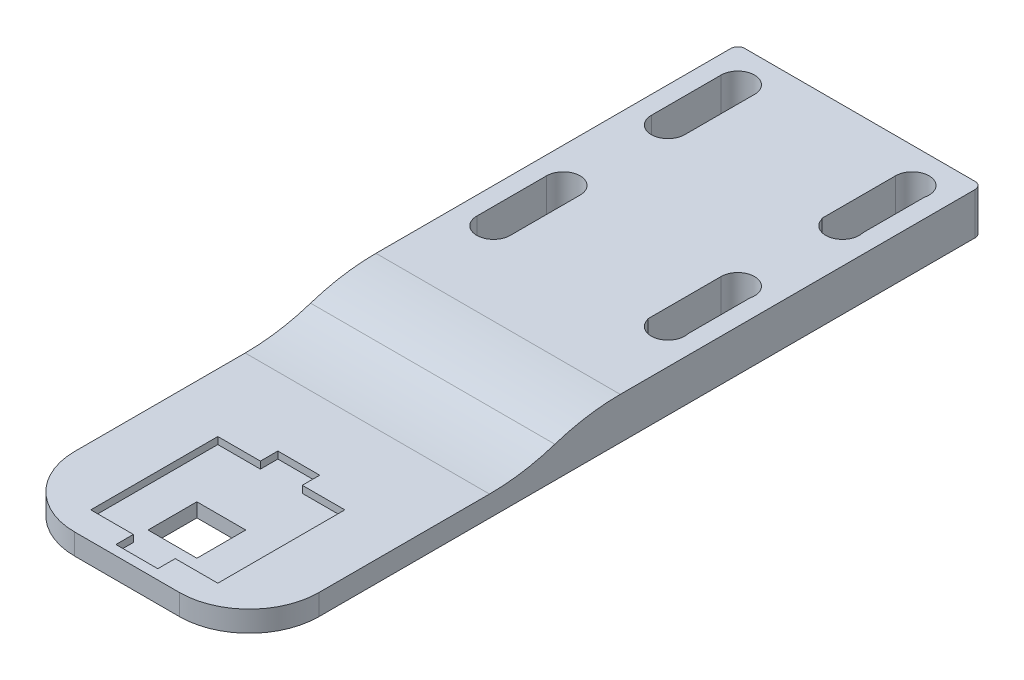
SolidWorks part; units mm, degrees
ref_plane "Front Plane" through (0, 0, 0) normal (0, 0, 1) x (1, 0, 0)
ref_plane "Top Plane" through (0, 0, 0) normal (0, 1, 0) x (1, 0, 0)
ref_plane "Right Plane" through (0, 0, 0) normal (1, 0, 0) x (0, 0, -1)
sketch "Sketch1" plane through (0, 0, 0) normal (0, 1, 0) x (1, 0, 0)
  line L1 (-17.3881, 19.9254) -> (17.6119, 19.9254)
  line L2 (-17.3881, 19.9254) -> (-17.3881, -85.0746)
  line L3 (-17.3881, -85.0746) -> (17.6119, -85.0746)
  line L4 (17.6119, 19.9254) -> (17.6119, -85.0746)
  dimension "D1" = 35
  dimension "D2" = 105
extrude "Boss-Extrude1" add sketch "Sketch1" along normal blind 6
sketch "Sketch2" plane through (0, 6, 0) normal (0, 1, 0) x (1, 0, 0)
  line L0 (17.6119, 19.9254) -> (-17.3881, 19.9254) construction
  line L1 (12.6119, -10.0746) -> (-12.3881, -10.0746)
  line L2 (12.6119, -10.0746) -> (12.6119, 14.9254)
  line L3 (12.6119, 14.9254) -> (-12.3881, 14.9254)
  line L4 (-12.3881, -10.0746) -> (-12.3881, 14.9254)
  line L5 (12.6119, -10.0746) -> (-12.3881, 14.9254) construction
  line L6 (12.6119, 14.9254) -> (-12.3881, -10.0746) construction
  point P0 (0.1119, 2.4254)
  point P7 (0.1119, 19.9254)
  dimension "D1" = 25
  dimension "D2" = 25
  dimension "D3" = 0
  dimension "D4" = 5
hole_wizard "M4 Clearance Hole1" positions "Sketch3" profile "Sketch4" hole size "M4" standard "ANSI Metric" end condition through all
sketch "Sketch3" plane through (0, 6, 0) normal (0, 1, 0) x (1, 0, 0)
  point P0 (-12.3881, 14.9254)
  point P3 (12.6119, 14.9254)
  point P6 (12.6119, -10.0746)
  point P9 (-12.3881, -10.0746)
sketch "Sketch4" plane through (-12.3881, 6, -14.9254) normal (1, 0, 0) x (0, 0, 1)
  line L0 (0, 0) -> (0, 6)
  line L1 (0, 6) -> (2.4, 6)
  line L2 (2.4, 6) -> (2.4, 0)
  line L5 (2.4, 0) -> (0, 0)
  line L11 (0, -6.35) -> (0, 107.95) construction
  dimension "Thru Hole Dia." = 4.8
  dimension "Thru Hole Depth" = 6
pattern_linear "LPattern2" count 2 spacing 10 along (0, 0, 1) of "M4 Clearance Hole1"
sketch "Sketch5" plane through (0, 6, 0) normal (0, 1, 0) x (1, 0, 0)
  line L1 (-14.7881, 14.9254) -> (-9.9881, 14.9254)
  line L2 (-14.7881, 14.9254) -> (-14.7881, 4.9254)
  line L3 (-14.7881, 4.9254) -> (-9.9881, 4.9254)
  line L4 (-9.9881, 14.9254) -> (-9.9881, 4.9254)
  line L5 (-14.7881, -10.0746) -> (-9.9881, -10.0746)
  line L6 (-14.7881, -10.0746) -> (-14.7881, -20.0746)
  line L7 (-14.7881, -20.0746) -> (-9.9881, -20.0746)
  line L8 (-9.9881, -10.0746) -> (-9.9881, -20.0746)
  line L9 (10.2119, 14.9254) -> (14.9426, 14.9254)
  line L10 (10.2119, 14.9254) -> (10.2119, 4.3527)
  line L11 (10.2119, 4.3527) -> (14.9426, 4.3527)
  line L12 (14.9426, 14.9254) -> (14.9426, 4.3527)
  line L13 (10.2119, -10.0746) -> (14.9426, -10.0746)
  line L14 (10.2119, -10.0746) -> (10.2119, -20.6473)
  line L15 (10.2119, -20.6473) -> (14.9426, -20.6473)
  line L16 (14.9426, -10.0746) -> (14.9426, -20.6473)
  circle A0 centre (-12.3881, 14.9254) radius 2.4 construction
  circle A1 centre (-12.3881, 4.9254) radius 2.4 construction
  circle A2 centre (-12.3881, -10.0746) radius 2.4 construction
  circle A3 centre (-12.3881, -20.0746) radius 2.4 construction
  circle A4 centre (12.6119, 14.9254) radius 2.4 construction
  circle A5 centre (12.6119, 4.9254) radius 2.4 construction
  circle A6 centre (12.6119, -10.0746) radius 2.4 construction
  circle A7 centre (12.6119, -20.0746) radius 2.4 construction
extrude "Cut-Extrude1" cut sketch "Sketch5" against normal through all
sketch "Sketch6" plane through (0, 6, 0) normal (0, 1, 0) x (1, 0, 0)
  line L1 (9.2119, -81.1746) -> (-8.9881, -81.1746)
  line L2 (9.2119, -81.1746) -> (9.2119, -62.9746)
  line L3 (9.2119, -62.9746) -> (-8.9881, -62.9746)
  line L4 (-8.9881, -81.1746) -> (-8.9881, -62.9746)
  line L5 (9.2119, -81.1746) -> (-8.9881, -62.9746) construction
  line L6 (9.2119, -62.9746) -> (-8.9881, -81.1746) construction
  line L9 (-17.3881, -85.0746) -> (17.6119, -85.0746) construction
  point P0 (0.1119, -72.0746)
  point P7 (0.1119, -85.0746)
  dimension "D1" = 18.2
  dimension "D2" = 18.2
  dimension "D3" = 13
  dimension "D4" = 0
extrude "Cut-Extrude2" cut sketch "Sketch6" against normal offset from surface (4 mm away) 2 up to face at (-12.3881, 0, 15.0746)
sketch "Sketch7" plane through (0, 2, 0) normal (0, 1, 0) x (1, 0, 0)
  line L0 (9.2119, -81.1746) -> (9.2119, -62.9746) construction
  line L1 (3.6119, -75.5746) -> (-3.3881, -75.5746)
  line L2 (3.6119, -75.5746) -> (3.6119, -68.5746)
  line L3 (3.6119, -68.5746) -> (-3.3881, -68.5746)
  line L4 (-3.3881, -75.5746) -> (-3.3881, -68.5746)
  line L5 (3.6119, -75.5746) -> (-3.3881, -68.5746) construction
  line L6 (3.6119, -68.5746) -> (-3.3881, -75.5746) construction
  line L7 (-17.3881, -85.0746) -> (17.6119, -85.0746) construction
  point P0 (0.1119, -72.0746)
  point P7 (9.2119, -72.0746)
  point P10 (0.1119, -85.0746)
  dimension "D1" = 0
  dimension "D2" = 0
  dimension "D3" = 7
  dimension "D4" = 7
extrude "Cut-Extrude3" cut sketch "Sketch7" against normal through all
sketch "Sketch8" plane through (0, 6, 0) normal (0, 1, 0) x (1, 0, 0)
  line L0 (9.2119, -62.9746) -> (-8.9881, -62.9746) construction
  line L1 (3.1119, -83.6746) -> (-2.8881, -83.6746)
  line L2 (3.1119, -83.6746) -> (3.1119, -60.4746)
  line L3 (3.1119, -60.4746) -> (-2.8881, -60.4746)
  line L4 (-2.8881, -83.6746) -> (-2.8881, -60.4746)
  line L5 (3.1119, -83.6746) -> (-2.8881, -60.4746) construction
  line L6 (3.1119, -60.4746) -> (-2.8881, -83.6746) construction
  line L7 (9.2119, -81.1746) -> (-8.9881, -81.1746) construction
  line L9 (3.6119, -68.5746) -> (-3.3881, -68.5746) construction
  point P0 (0.1119, -72.0746)
  point P11 (0.1119, -68.5746)
  dimension "D1" = 2.5
  dimension "D2" = 2.5
  dimension "D3" = 6
  dimension "D4" = 0
extrude "Cut-Extrude4" cut sketch "Sketch8" against normal up to surface (4 mm away) up to face at (0.1119, 2, 72.0746)
fillet "Fillet1" radius 10 2 edges at (17.6119, 3, 85.0746) (-17.3881, 3, 85.0746)
sketch "Sketch9" plane through (0, 0, 0) normal (0, -1, 0) x (1, 0, 0)
  line L0 (-17.3881, -19.9254) -> (-17.3881, 75.0746) construction
  line L1 (-17.3881, 37.5746) -> (19.6619, 37.5746)
  line L2 (-17.3881, 37.5746) -> (-17.3881, 85.0746)
  line L3 (-17.3881, 85.0746) -> (19.6619, 85.0746)
  line L4 (19.6619, 37.5746) -> (19.6619, 85.0746)
  line L5 (-7.3881, 85.0746) -> (7.6119, 85.0746) construction
  line L6 (9.2119, 62.9746) -> (3.1119, 62.9746) construction
  dimension "D1" = 25.4
  dimension "D2" = 0
extrude "Cut-Extrude5" cut sketch "Sketch9" along normal offset from surface (3 mm away) 3 from surface up to face at (0.1119, 0, 72.0746) starting at face at (0.1119, 6, 72.0746)
fillet "Fillet2" radius 30 1 edges at (0.1119, 3, 37.5746)
fillet "Fillet3" radius 30 1 edges at (0.1119, 6, 37.5746)
fillet "Fillet4" radius 1 2 edges at (17.6119, 3, -19.9254) (-17.3881, 3, -19.9254)
ref_plane "Plane11" through (3.1119, 3, 83.6746) normal (-1, 0, 0) x (0, 0, 1)
sketch "Sketch14" plane through (-3.3881, 0, 0) normal (1, 0, 0) x (0, 0, -1)
  line L1 (-68.5746, 0) -> (-75.5746, 0)
  line L2 (-68.5746, 0) -> (-68.5746, 2)
  line L3 (-68.5746, 2) -> (-75.5746, 2)
  line L4 (-75.5746, 0) -> (-75.5746, 2)
extrude "Boss-Extrude2" add sketch "Sketch14" along normal up to surface (7 mm away) contours L2 L1 L4 L3 up to face at (3.6119, 1, 72.0746)
sketch "Sketch16" plane through (0, 3, 0) normal (0, 1, 0) x (1, 0, 0)
  line L0 (-17.3881, -75.0746) -> (17.6119, -75.0746)
  line L1 (-17.3881, -75.0746) -> (-17.3881, -50.6513) construction
  line L2 (17.6119, -75.0746) -> (17.6119, -50.6513) construction
  line L3 (0.1119, -75.0746) -> (0.1119, -85.0746)
  line L4 (-3.3881, -78.5746) -> (3.6119, -78.5746)
  line L5 (-3.3881, -78.5746) -> (-3.3881, -71.5746)
  line L6 (-3.3881, -71.5746) -> (3.6119, -71.5746)
  line L7 (3.6119, -78.5746) -> (3.6119, -71.5746)
  line L8 (-3.3881, -78.5746) -> (3.6119, -71.5746) construction
  line L9 (-3.3881, -71.5746) -> (3.6119, -78.5746) construction
  line L10 (7.6119, -85.0746) -> (-7.3881, -85.0746) construction
  point P6 (0.1119, -75.0746)
extrude "Cut-Extrude6" cut sketch "Sketch16" against normal blind 10 contours L5 L4 L7 L6
